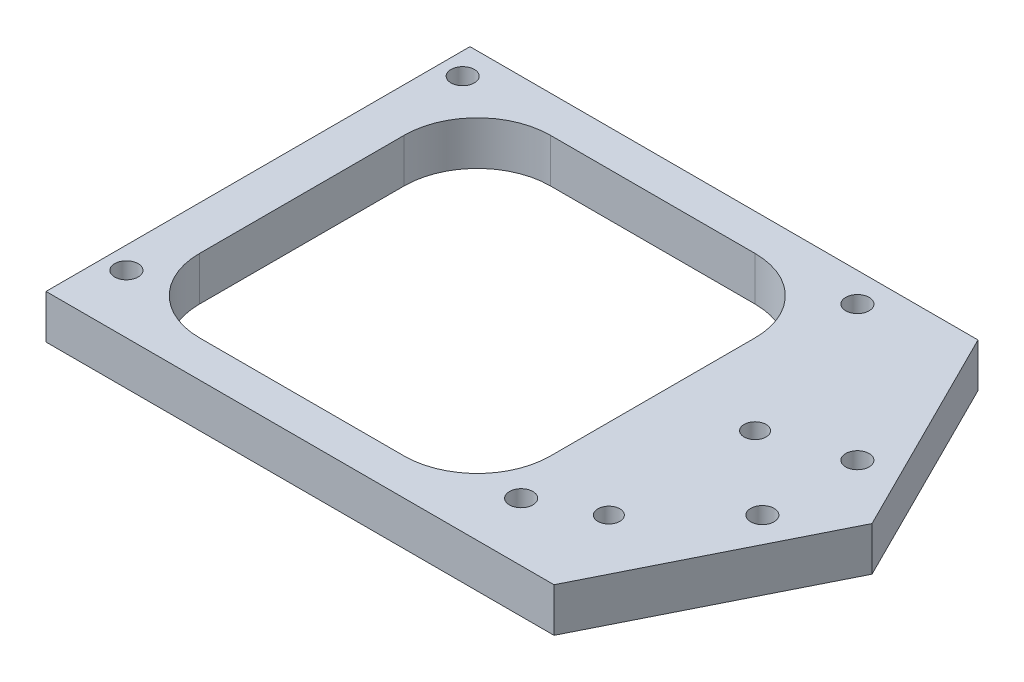
SolidWorks part; units mm, degrees
material "6061-T6 (SS)"
ref_plane "Front Plane" through (0, 0, 0) normal (0, 0, 1) x (1, 0, 0)
ref_plane "Top Plane" through (0, 0, 0) normal (0, 1, 0) x (1, 0, 0)
ref_plane "Right Plane" through (0, 0, 0) normal (1, 0, 0) x (0, 0, -1)
sketch "Sketch1" plane through (0, 0, 0) normal (0, 1, 0) x (1, 0, 0)
  line L0 (0, 14.5) -> (42, 14.5) construction
  line L1 (0, 0) -> (34.7484, 0)
  line L2 (0, 0) -> (0, 29)
  line L5 (42, 14.5) -> (34.7484, 29)
  line L6 (42, 14.5) -> (34.7484, 0)
  line L7 (0, 29) -> (34.7484, 29)
  dimension "D1" = 29
  dimension "D2" = 42
  dimension "D3" = 63.43
extrude "Boss-Extrude1" add sketch "Sketch1" along normal mid plane 3
sketch "Sketch2" plane through (0, 0, 0) normal (0, 1, 0) x (1, 0, 0)
  line L0 (0, 29) -> (0, 0) construction
  line L1 (3, 26.5) -> (27, 26.5)
  line L2 (3, 26.5) -> (3, 2.5)
  line L4 (27, 26.5) -> (27, 2.5)
  line L5 (0, 14.5) -> (42, 14.5) construction
  line L6 (34.7484, 29) -> (0, 29) construction
  line L7 (3, 2.5) -> (27, 2.5)
  point P14 (27, 14.5)
  point P15 (3, 14.5)
  dimension "D1" = 3
  dimension "D2" = 24
  dimension "D3" = 2.5
extrude "Cut-Extrude1" cut sketch "Sketch2" against normal through all both and the other way through all
fillet "Fillet1" radius 5 4 edges at (3, 0, -26.5) (27, 0, -26.5) (27, 0, -2.5) (3, 0, -2.5)
sketch "Sketch5" plane through (0, 1.5, 0) normal (0, 1, 0) x (1, 0, 0)
  line L0 (1.5, 27) -> (28.5, 27) construction
  line L1 (28.5, 27) -> (28.5, 4) construction
  line L2 (28.5, 4) -> (1.5, 4) construction
  line L3 (1.5, 4) -> (1.5, 27) construction
  line L4 (42, 14.5) -> (0, 14.5) construction
  line L7 (34.7484, 29) -> (0, 29) construction
  line L8 (0, 29) -> (0, 0) construction
  point P8 (37.7484, 11.25)
  point P16 (37.7484, 17.75)
  dimension "D1" = 3.25
  dimension "D2" = 2
  dimension "D3" = 1.5
  dimension "D4" = 23
  dimension "D5" = 27
  dimension "D6" = 37.7484
hole_wizard "M2x0.4 Tapped Hole1" positions "3DSketch4" profile "Sketch8" tap size "M2x0.4" standard "ANSI Metric" end condition through all
sketch3d "3DSketch4"
  point P0 (1.5, 1.5, -27)
  point P3 (28.5, 1.5, -27)
  point P6 (37.7484, 1.5, -17.75)
  point P9 (37.7484, 1.5, -11.25)
  point P12 (28.5, 1.5, -4)
  point P15 (1.5, 1.5, -4)
sketch "Sketch8" plane through (1.5, 1.5, -27) normal (1, 0, 0) x (0, 0, 1)
  line L0 (0, 0) -> (0, 3)
  line L1 (0, 3) -> (0.8, 3)
  line L2 (0.8, 3) -> (0.8, 0)
  line L5 (0.8, 0) -> (0, 0)
  line L11 (0, -6.35) -> (0, 107.95) construction
  dimension "Thru Tap Drill Dia." = 1.6
  dimension "Thru Tap Drill Depth" = 3
cosmetic thread "Hole Thread1" parameters "D2"=2
cosmetic thread "Hole Thread2" parameters "D2"=2
cosmetic thread "Hole Thread3" parameters "D2"=2
cosmetic thread "Hole Thread4" parameters "D2"=2
cosmetic thread "Hole Thread5" parameters "D2"=2
cosmetic thread "Hole Thread6" parameters "D2"=2
sketch "Sketch9" plane through (0, 1.5, 0) normal (0, 1, 0) x (1, 0, 0)
  line L3 (0, 0) -> (34.7484, 0) construction
  line L5 (0, 29) -> (0, 0) construction
  point P0 (32.5, 16)
  point P1 (32.5, 6)
  dimension "D1" = 32.5
  dimension "D2" = 16
  dimension "D3" = 6
  dimension "D4" = 32.5
hole_wizard "Ø1.5mm Dowel Hole1" positions "3DSketch5" profile "Sketch10" hole size "Ø1.5" standard "ANSI Metric" end condition through all
sketch3d "3DSketch5"
  point P0 (32.5, 1.5, -16)
  point P3 (32.5, 1.5, -6)
sketch "Sketch10" plane through (32.5, 1.5, -16) normal (1, 0, 0) x (0, 0, 1)
  line L0 (0, 0) -> (0, 3)
  line L1 (0, 3) -> (0.75, 3)
  line L2 (0.75, 3) -> (0.75, 0)
  line L5 (0.75, 0) -> (0, 0)
  line L11 (0, -6.35) -> (0, 107.95) construction
  dimension "Thru Hole Dia." = 1.5
  dimension "Thru Hole Depth" = 3
